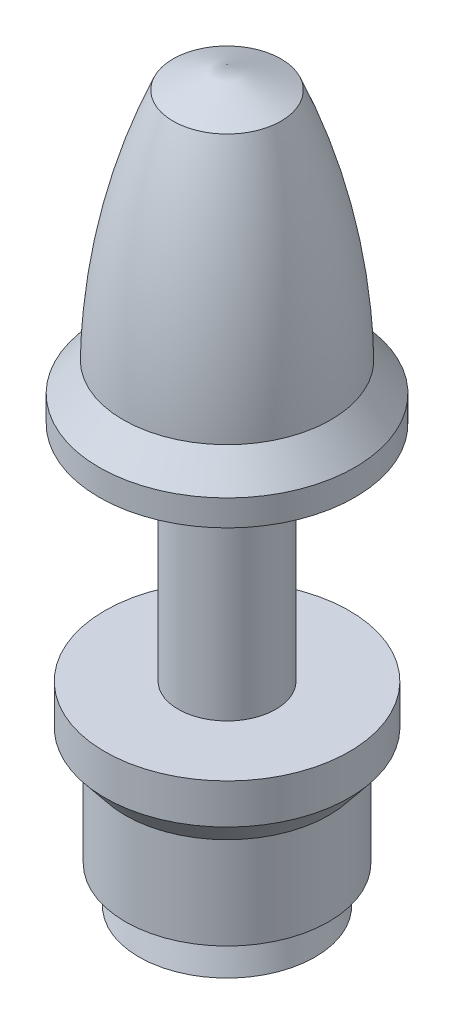
SolidWorks part; units mm, degrees
ref_plane "Front Plane" through (0, 0, 0) normal (0, 0, 1) x (1, 0, 0)
ref_plane "Top Plane" through (0, 0, 0) normal (0, 1, 0) x (1, 0, 0)
ref_plane "Right Plane" through (0, 0, 0) normal (1, 0, 0) x (0, 0, -1)
ref_axis "Axis1" through (0, 25.5099, 0) along (0, -1, 0)
sketch "Sketch1" plane through (0, 0, 0) normal (0, 0, 1) x (1, 0, 0)
  line L0 (0, 0) -> (4.3117, 0)
  line L3 (4.9784, 1.8288) -> (4.9784, 6.3373)
  line L4 (4.9784, 6.3373) -> (5.9817, 7.5819)
  line L5 (5.9817, 7.5819) -> (5.9817, 9.5377)
  line L6 (5.9817, 9.5377) -> (2.3876, 9.5377)
  line L7 (2.3876, 9.5377) -> (2.3876, 24.2951)
  line L8 (2.3876, 24.2951) -> (0, 24.2951)
  line L9 (0, 24.2951) -> (0, 0)
  line L10 (4.9784, 1.8288) -> (3.81, 1.8288)
  line L11 (3.81, 1.8288) -> (4.3117, 0)
  dimension "D1" = 9.5377
  dimension "D2" = 24.2951
  dimension "D3" = 1.9558
  dimension "D4" = 3.81
  dimension "D5" = 1.2446
  dimension "D6" = 4.9784
  dimension "D7" = 5.9817
  dimension "D8" = 4.3117
  dimension "D9" = 4.5085
  dimension "D10" = 2.3876
revolve "Revolve1" add sketch "Sketch1" angle 360 about L9
sketch "Sketch2" plane through (0, 0, 0) normal (0, -1, 0) x (1, 0, 0)
  circle A0 centre (0, 0) radius 1.5748
  dimension "D1" = 3.1496
extrude "Cut-Extrude1" cut sketch "Sketch2" against normal blind 2.54
sketch "Sketch3" plane through (0, 0, 0) normal (0, 0, 1) x (1, 0, 0)
  line L0 (0, 35.6743) -> (2.6416, 34.5948)
  line L1 (0, 25.5099) -> (0, -1.2148) construction
  line L2 (0, -6.5799) -> (0, 6.5799) construction
  line L4 (0, 20.4597) -> (6.2611, 20.4597)
  line L5 (6.2611, 20.4597) -> (6.2611, 21.7297)
  line L6 (6.2611, 21.7297) -> (5.08, 23.1521)
  line L7 (0, 35.6743) -> (0, 20.4597)
  line L8 (5.9817, 9.5377) -> (-5.9817, 9.5377) construction
  arc A0 (2.6416, 34.5948) -> (5.08, 23.1521) centre (-25.8221, 22.5481) cw
  dimension "D9" = 30.908
  dimension "D1" = 15.2146
  dimension "D2" = 1.0795
  dimension "D3" = 2.6416
  dimension "D4" = 10.922
  dimension "D5" = 6.2611
  dimension "D6" = 1.27
  dimension "D7" = 1.4224
  dimension "D8" = 5.08
revolve "Revolve2" add sketch "Sketch3" angle 360 about L7
